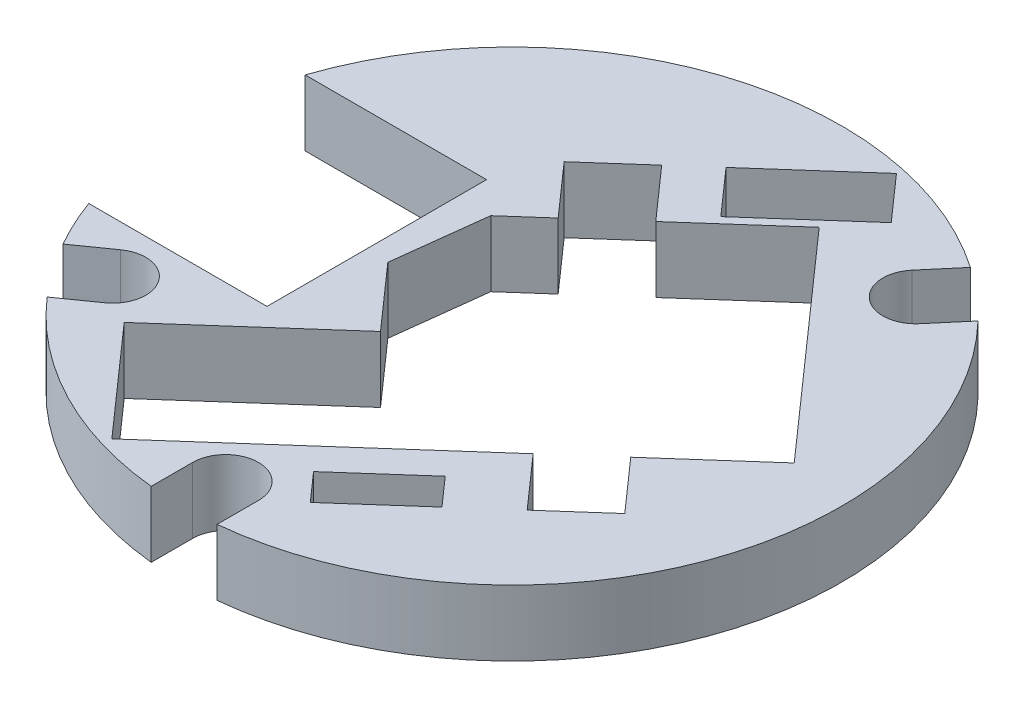
SolidWorks part; units mm, degrees
ref_plane "Front" through (0, 0, 0) normal (0, 0, 1) x (1, 0, 0)
ref_plane "Top" through (0, 0, 0) normal (0, 1, 0) x (1, 0, 0)
ref_plane "Right" through (0, 0, 0) normal (1, 0, 0) x (0, 0, -1)
sketch "Sketch1" plane through (0, 0, 0) normal (0, 1, 0) x (1, 0, 0)
  arc A0 (16.9841, 5.5245) -> (-17.1812, 4.8768) centre (0, 0) ccw
  arc A1 (-17.0607, -5.2832) -> (16.9841, -5.5245) centre (0, 0) ccw
  line B0 (-6.0563, 4.8768) -> (-17.1812, 4.8768)
  line B1 (-6.0563, 4.8768) -> (-6.0563, -5.2832)
  line B2 (-17.0607, -5.2832) -> (-6.0563, -5.2832)
  line B3 (-8.7203, -9.2308) -> (-2.4254, -3.6624)
  line B4 (-8.7203, -9.2308) -> (-4.3384, -14.1843)
  line B5 (6.0088, -5.0313) -> (-4.3384, -14.1843)
  line B6 (1.6411, -10.8279) -> (2.8023, -12.1406)
  line B7 (4.8753, -7.967) -> (1.6411, -10.8279)
  line B8 (2.8023, -12.1406) -> (6.0365, -9.2797)
  line B9 (6.0365, -9.2797) -> (4.8753, -7.967)
  line B10 (8.1292, -7.4285) -> (6.0088, -5.0313)
  line B11 (10.5264, -5.308) -> (8.1292, -7.4285)
  line B12 (8.4059, -2.9109) -> (10.5264, -5.308)
  line B13 (8.4059, -2.9109) -> (12.4201, 0.64)
  line B14 (12.4201, 0.64) -> (3.5512, 10.6661)
  line B15 (-0.463, 7.1152) -> (3.5512, 10.6661)
  line B16 (-2.5835, 9.5123) -> (-0.463, 7.1152)
  line B17 (-4.9806, 7.3918) -> (-2.5835, 9.5123)
  line B18 (-4.9806, 7.3918) -> (-2.8601, 4.9947)
  line B19 (-2.8601, 4.9947) -> (-4.5153, 3.5306)
  line B20 (-4.5153, 3.5306) -> (-5.0276, -0.7207)
  line B21 (-5.0276, -0.7207) -> (-2.4254, -3.6624)
  line B22 (-1.0044, 10.9091) -> (0.8468, 8.8164)
  line B23 (3.181, 14.6115) -> (-1.0044, 10.9091)
  line B24 (5.0322, 12.5188) -> (3.181, 14.6115)
  line B25 (0.8468, 8.8164) -> (5.0322, 12.5188)
  line B26 (16.9841, -5.5245) -> (16.9841, 5.5245)
  circle B27 centre (-10.8325, -7.6454) radius 1.143
  circle B28 centre (0, -13.2588) radius 1.143
  circle B29 centre (8.579, 10.1092) radius 1.143
sketch_block_instance "Ai_Pulsar_block_2-1"
sketch_block "Ai_Pulsar_block_2"
extrude "Boss-Extrude1" add sketch "Sketch1" along normal mid plane 3.048 contours A1 B26 A0 B0 B1 B2 B29 B28 B27 B9 B8 B6 B7 B21 B20 B19 B18 B17 B16 B15 B14 B13 B12 B11 B10 B5 B4 B3 B25 B22 B23 B24 region at (16.4898, 0, 0)
sketch "Sketch2" plane through (0, 1.524, 0) normal (0, 1, 0) x (1, 0, 0)
  line L0 (-1.524, -13.2588) -> (-1.524, -17.7948)
  line L1 (1.524, -13.2588) -> (1.524, -17.7948)
  line L2 (7.4171, 11.0953) -> (10.3521, 14.5538)
  line L3 (9.741, 9.1231) -> (12.676, 12.5816)
  line L4 (-11.7113, -6.4003) -> (-15.4173, -9.0159)
  line L5 (-9.9537, -8.8905) -> (-13.6597, -11.5061)
  line L6 (0, 0) -> (8.579, 10.1092) construction
  line L7 (0, 0) -> (0, -13.2588) construction
  line L8 (0, 0) -> (-10.8325, -7.6454) construction
  circle A0 centre (8.579, 10.1092) radius 1.524
  circle A1 centre (0, -13.2588) radius 1.524
  circle A2 centre (-10.8325, -7.6454) radius 1.524
  arc A3 (-17.0607, -5.2832) -> (16.9841, -5.5245) centre (0, 0) ccw construction
  arc A4 (16.9841, 5.5245) -> (-17.1812, 4.8768) centre (0, 0) ccw construction
  circle M1 centre (8.579, 10.1092) radius 1.143
  circle M2 centre (0, -13.2588) radius 1.143
  circle M3 centre (-10.8325, -7.6454) radius 1.143
  arc M27 (-17.0607, -5.2832) -> (16.9841, -5.5245) centre (0, 0) ccw
  arc M29 (16.9841, 5.5245) -> (-17.1812, 4.8768) centre (0, 0) ccw
  dimension "D1" = 3.048
extrude "Cut-Extrude1" cut sketch "Sketch2" against normal through all contours A2 M3 | A2 L4 L5 M27 | A1 L0 L1 M27 | A1 M2 | A0 L3 L2 M29 | A0 M1 region at (0, 1.524, 16.13) region at (-13.1783, 1.524, 9.301) region at (0, 1.524, 11.7779) region at (-12.0424, 1.524, 8.4993) region at (10.4368, 1.524, -12.2983) region at (9.0894, 1.524, -11.4994)
sketch "Sketch3" plane through (0, 1.524, 0) normal (0, 1, 0) x (1, 0, 0)
  line L0 (-12.1294, 17.1857) -> (12.1294, -17.1857) construction
  line L1 (-10.8325, -7.6454) -> (0, 0) construction
  line L2 (0, 0) -> (0, -13.2588) construction
  line L3 (0, 0) -> (8.579, 10.1092) construction
  circle A0 centre (-12.1294, 17.1857) radius 1.143
  circle A1 centre (12.1294, -17.1857) radius 1.143
  circle A2 centre (-12.1294, 17.1857) radius 3.175
  arc A3 (10.3521, 14.5538) -> (-17.1812, 4.8768) centre (0, 0) ccw construction
  arc A4 (1.524, -17.7948) -> (16.9841, -5.5245) centre (0, 0) ccw construction
  arc A5 (10.3521, 14.5538) -> (-17.1812, 4.8768) centre (0, 0) ccw
  arc A6 (1.524, -17.7948) -> (16.9841, -5.5245) centre (0, 0) ccw
  arc A7 (-13.2143, 12.015) -> (-13.6243, 14.3847) centre (-14.3419, 13.0402) ccw
  arc A8 (-8.9894, 17.656) -> (-6.8939, 16.4758) centre (-7.4822, 17.8817) ccw
  circle A9 centre (12.1294, -17.1857) radius 3.175
  arc A10 (8.9894, -17.656) -> (6.8939, -16.4758) centre (7.4822, -17.8817) ccw
  arc A11 (13.2143, -12.015) -> (13.6243, -14.3847) centre (14.3419, -13.0402) ccw
  dimension "D1" = 2.286
  dimension "D2" = 6.35
  dimension "D3" = 3.048
sketch "Sketch4" plane through (0, 1.524, 0) normal (0, 1, 0) x (1, 0, 0)
  circle A0 centre (0, 0) radius 15.2527
  circle A1 centre (0, 0) radius 20.6955
  dimension "D1" = 30.5054
extrude "Cut-Extrude2" cut sketch "Sketch4" against normal through all
